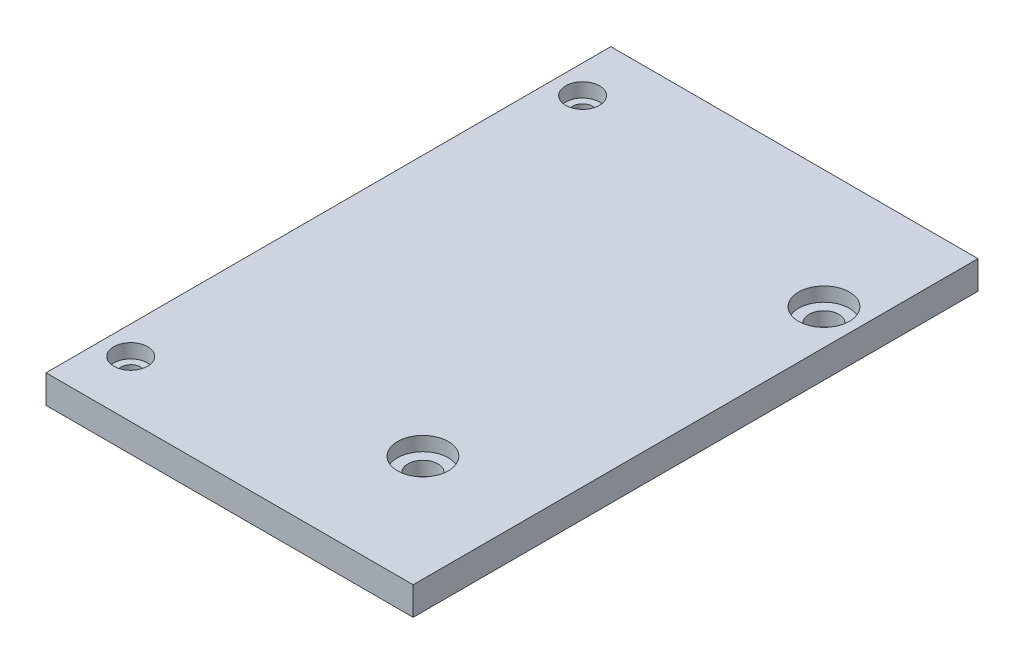
SolidWorks part; units mm, degrees
ref_plane "Front Plane" through (0, 0, 0) normal (0, 0, 1) x (1, 0, 0)
ref_plane "Top Plane" through (0, 0, 0) normal (0, 1, 0) x (1, 0, 0)
ref_plane "Right Plane" through (0, 0, 0) normal (1, 0, 0) x (0, 0, -1)
sketch "Sketch2" plane through (0, 0, 0) normal (0, 1, 0) x (1, 0, 0)
  line L1 (-32.5, 50) -> (32.5, 50)
  line L2 (-32.5, 50) -> (-32.5, -50)
  line L3 (-32.5, -50) -> (32.5, -50)
  line L4 (32.5, 50) -> (32.5, -50)
  line L5 (-32.5, 50) -> (32.5, -50) construction
  line L6 (-32.5, -50) -> (32.5, 50) construction
  circle A0 centre (-27.5, 40) radius 1.75
  circle A1 centre (-27.5, -40) radius 1.75
  circle A2 centre (26.23, 29) radius 2.65
  circle A3 centre (13.65, -29.42) radius 2.65
  point P0 (0, 0)
  dimension "D3" = 3.5
  dimension "D4" = 5
  dimension "D8" = 5.3
  dimension "D9" = 5.3
  dimension "D1" = 65
  dimension "D2" = 100
  dimension "D5" = 5
  dimension "D6" = 10
  dimension "D7" = 10
  dimension "D10" = 18.85
  dimension "D11" = 20.58
  dimension "D12" = 6.27
  dimension "D13" = 21
extrude "Boss-Extrude1" add sketch "Sketch2" along normal blind 5
sketch "Sketch3" plane through (0, 5, 0) normal (0, 1, 0) x (1, 0, 0)
  circle A0 centre (26.23, 29) radius 4.5
  circle A1 centre (13.65, -29.42) radius 4.5
  circle A2 centre (-27.5, 40) radius 3
  circle A3 centre (-27.5, -40) radius 3
  dimension "D1" = 9
  dimension "D2" = 9
  dimension "D3" = 6
  dimension "D4" = 6
extrude "Cut-Extrude1" cut sketch "Sketch3" against normal blind 2.5
